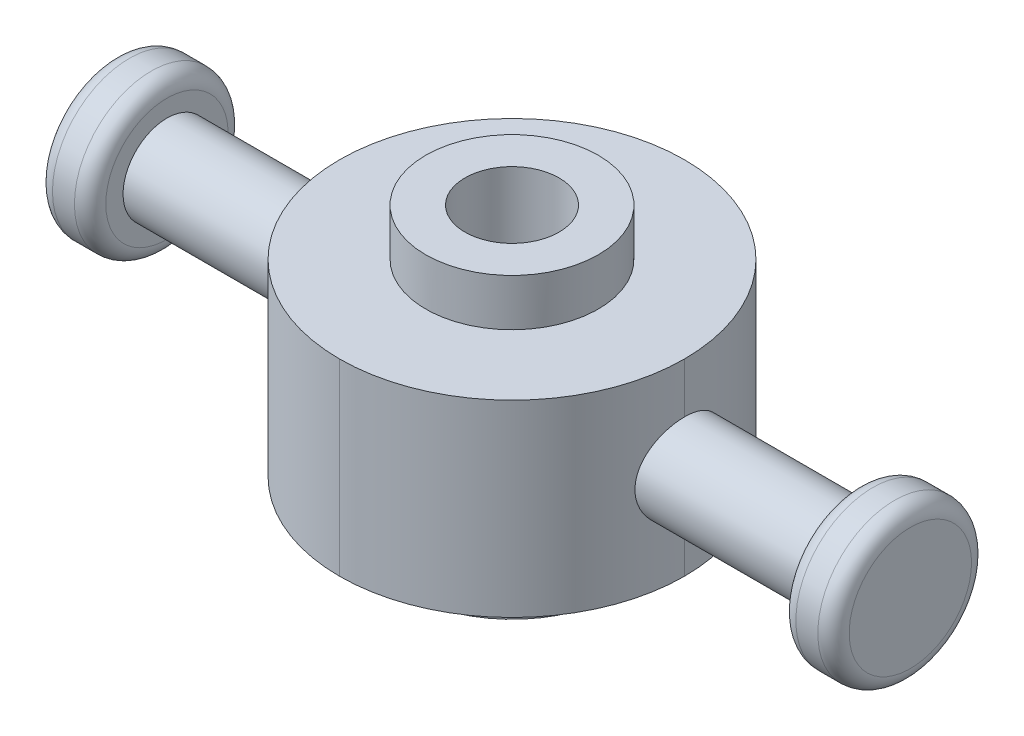
SolidWorks part; units mm, degrees
ref_plane "Front Plane" through (0, 0, 0) normal (0, 0, 1) x (1, 0, 0)
ref_plane "Top Plane" through (0, 0, 0) normal (0, 1, 0) x (1, 0, 0)
ref_plane "Right Plane" through (0, 0, 0) normal (1, 0, 0) x (0, 0, -1)
sketch "Sketch1" plane through (0, 0, 0) normal (0, 1, 0) x (1, 0, 0)
  line L1 (0, 0) -> (11, 0)
  line L2 (0, 0) -> (0, 11)
  line L3 (0, 11) -> (11, 11)
  line L4 (11, 0) -> (11, 11)
  dimension "D1" = 11
  dimension "D2" = 11
extrude "Extrude1" add sketch "Sketch1" along normal blind 6
sketch "Sketch2" plane through (11, 0, 0) normal (1, 0, 0) x (0, 0, -1)
  line L0 (0, 6) -> (0, 0) construction
  line L1 (0, 0) -> (11, 0) construction
  circle A0 centre (5.5, 3) radius 1.4
  dimension "D1" = 2.8
  dimension "D2" = 5.5
  dimension "D3" = 3
extrude "Extrude2" add sketch "Sketch2" along normal blind 5.5
sketch "Sketch3" plane through (0, 0, 0) normal (-1, 0, 0) x (0, 0, 1)
  line L0 (0, 6) -> (0, 0) construction
  line L1 (-11, 6) -> (0, 6) construction
  circle A0 centre (-5.5, 3) radius 1.4
  dimension "D1" = 2.8
  dimension "D2" = 5.5
  dimension "D3" = 3
extrude "Extrude3" add sketch "Sketch3" along normal blind 5.5
sketch "Sketch4" plane through (0, 6, 0) normal (0, 1, 0) x (1, 0, 0)
  line L0 (11, 11) -> (0, 11) construction
  line L1 (11, 0) -> (11, 11) construction
  circle A0 centre (5.5, 5.5) radius 2.75
  dimension "D1" = 5.5
  dimension "D2" = 5.5
  dimension "D3" = 5.5
extrude "Extrude4" add sketch "Sketch4" along normal blind 1.5
sketch "Sketch5" plane through (0, 0, 0) normal (0, -1, 0) x (1, 0, 0)
  line L0 (0, 0) -> (11, 0) construction
  line L1 (11, 0) -> (11, -11) construction
  circle A0 centre (5.5, -5.5) radius 3.45
  dimension "D1" = 6.9
  dimension "D2" = 5.5
  dimension "D3" = 5.5
extrude "Extrude5" add sketch "Sketch5" along normal blind 1.5
sketch "Sketch6" plane through (16.5, 0, 0) normal (1, 0, 0) x (0, 0, -1)
  circle A0 centre (5.5, 3) radius 2.45
  dimension "D1" = 4.9
extrude "Extrude6" add sketch "Sketch6" along normal blind 1.7
sketch "Sketch7" plane through (-5.5, 0, 0) normal (-1, 0, 0) x (0, 0, 1)
  circle A0 centre (-5.5, 3) radius 2.45
  dimension "D1" = 4.9
extrude "Extrude7" add sketch "Sketch7" along normal blind 1.7
sketch "Sketch8" plane through (0, -1.5, 0) normal (0, -1, 0) x (1, 0, 0)
  circle A0 centre (5.5, -5.5) radius 1.5
  dimension "D1" = 3
extrude "Extrude8" cut sketch "Sketch8" against normal through all
fillet "Fillet1" radius 5.5 4 edges at (0, 3, 0) (0, 3, -11) (11, 3, -11) (11, 3, 0)
fillet "Fillet3" radius 0.5 4 edges at (-7.2, 3, -3.05) (18.2, 3, -7.95) (16.5, 3, -7.95) (-5.5, 3, -3.05)
equation "\"D2@Sketch1\" = \"D1@Sketch1\""
equation "\"D3@Sketch4\" = \"D2@Sketch4\""
equation "\"D3@Sketch5\" = \"D2@Sketch5\""
